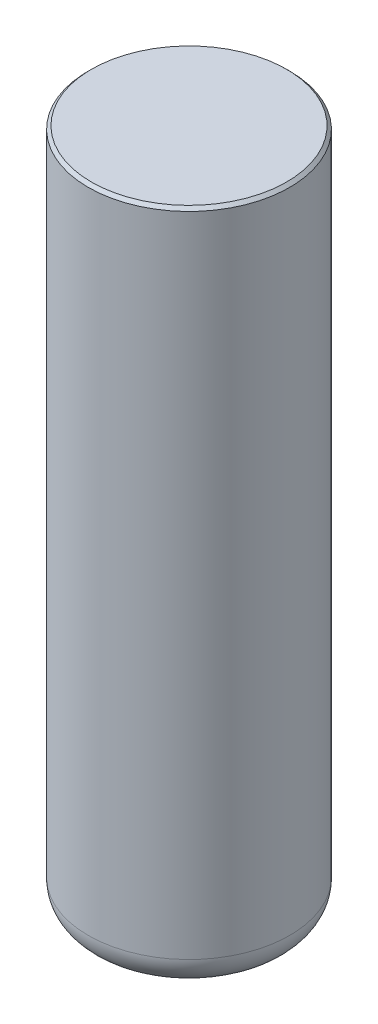
SolidWorks part; units mm, degrees
material "6061-T6 Aluminum"
ref_plane "Front Plane" through (0, 0, 0) normal (0, 0, 1) x (1, 0, 0)
ref_plane "Top Plane" through (0, 0, 0) normal (0, 1, 0) x (1, 0, 0)
ref_plane "Right Plane" through (0, 0, 0) normal (1, 0, 0) x (0, 0, -1)
sketch "Sketch1" plane through (0, 0, 0) normal (0, 1, 0) x (1, 0, 0)
  circle A0 centre (0, 0) radius 32.5
  point P2 (0, 0)
  dimension "D1" = 65
extrude "Boss-Extrude1" add sketch "Sketch1" along normal blind 220
fillet "Fillet1" radius 10 1 edges at (0, 0, 32.5)
chamfer "Chamfer1" distance 1 angle 45 1 edges at (0, 220, 32.5)
